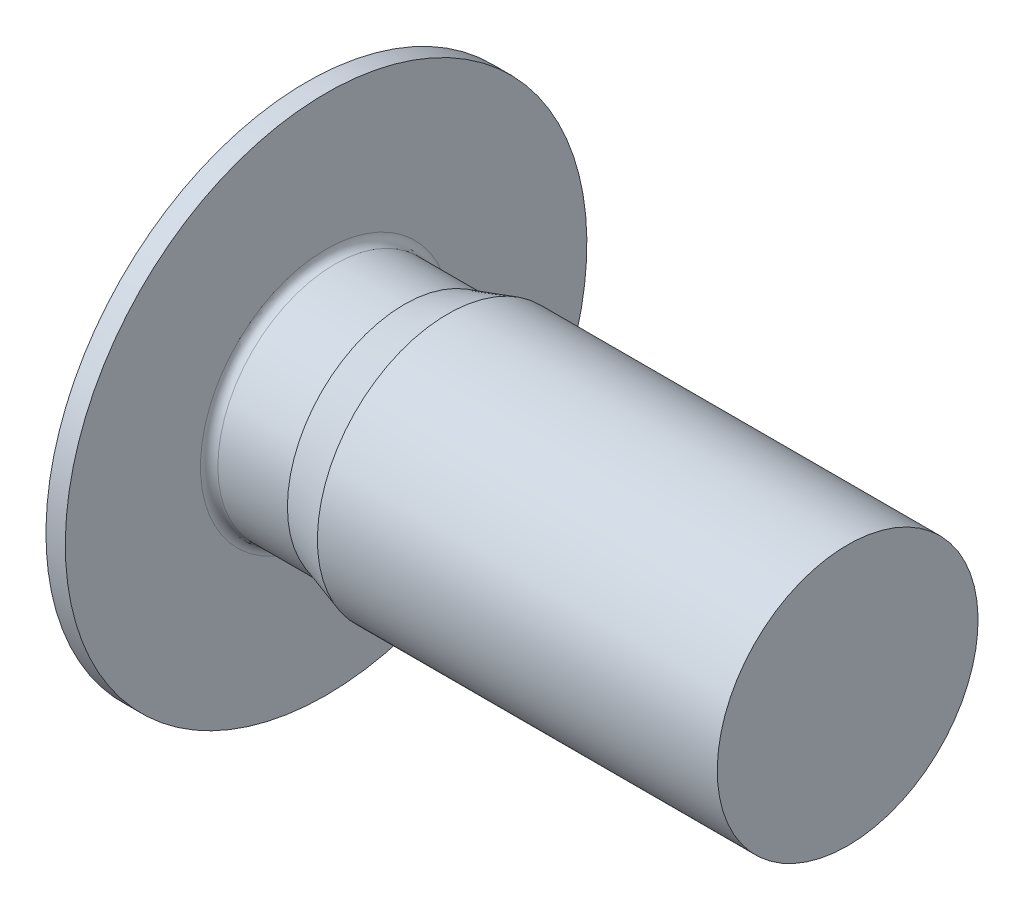
SolidWorks part; units mm, degrees
material "SCM435"
ref_plane "Front Plane" through (0, 0, 0) normal (0, 0, 1) x (1, 0, 0)
ref_plane "Top Plane" through (0, 0, 0) normal (0, 1, 0) x (1, 0, 0)
ref_plane "Right Plane" through (0, 0, 0) normal (1, 0, 0) x (0, 0, -1)
sketch "Sketch1" plane through (0, 0, 0) normal (0, 0, 1) x (1, 0, 0)
  line L0 (-0.8, 0) -> (6, 0) construction
  line L1 (-0.8, 0) -> (-0.8, 2)
  line L2 (-0.2226, 3) -> (0, 3)
  line L3 (0, 3) -> (0, 1.345)
  line L4 (1.4, 1.5) -> (6, 1.5)
  line L5 (6, 1.5) -> (6, 0)
  line L6 (6, 0) -> (-0.8, 0)
  line L7 (1.4, 1.5) -> (0.9, 1.345)
  line L8 (0.9, 1.345) -> (0, 1.345)
  line L9 (-0.2226, 3) -> (-0.8, 2)
  line L10 (-0.8, 0) -> (6, 0) construction
  dimension "A" = 6
  dimension "M" = 3
  dimension "L" = 6
  dimension "E" = 0.8
  dimension "FIX_1" = 30
  dimension "MSM_1" = 4
  dimension "MSM_2" = 2.69
  dimension "MSM_3" = 0.5
  dimension "E_s" = 1.4
revolve "Revolve1" add sketch "Sketch1" angle 360 about L0
cosmetic thread "Thread1" parameters "ATL_1"=4.6, "ATD"=2.459
fillet "Fillet1" radius 0.1 1 edges at (0, -1.345, 0)
sketch "Sketch2" plane through (-0.8, 0, 0) normal (-1, 0, 0) x (0, 0, 1)
  line L1 (0, 0.866) -> (-0.75, 0.433)
  line L2 (-0.75, 0.433) -> (-0.75, -0.433)
  line L3 (-0.75, -0.433) -> (0, -0.866)
  line L4 (0, -0.866) -> (0.75, -0.433)
  line L5 (0.75, -0.433) -> (0.75, 0.433)
  line L6 (0.75, 0.433) -> (0, 0.866)
  circle A0 centre (0, 0) radius 0.75 construction
  dimension "B" = 1.5
extrude "Cut-Extrude1" cut sketch "Sketch2" against normal blind 2
sketch "Sketch3" plane through (0, 0, 0) normal (0, 0, 1) x (1, 0, 0)
  line L0 (1.2, 0) -> (1.6506, 0) construction
  line L1 (1.2, 0) -> (1.2, 0.75)
  line L2 (1.2, 0.75) -> (1.6506, 0)
  line L3 (1.6506, 0) -> (1.2, 0)
  line L5 (1.2, 0.433) -> (1.2, -0.433) construction
  dimension "FIX_3" = 59
  dimension "B" = 1.5
revolve "Cut-Revolve1" cut sketch "Sketch3" angle 360 about L0
equation "\"ATL_1@Thread1\" = \"L@Sketch1\" - \"E_s@Sketch1\""
